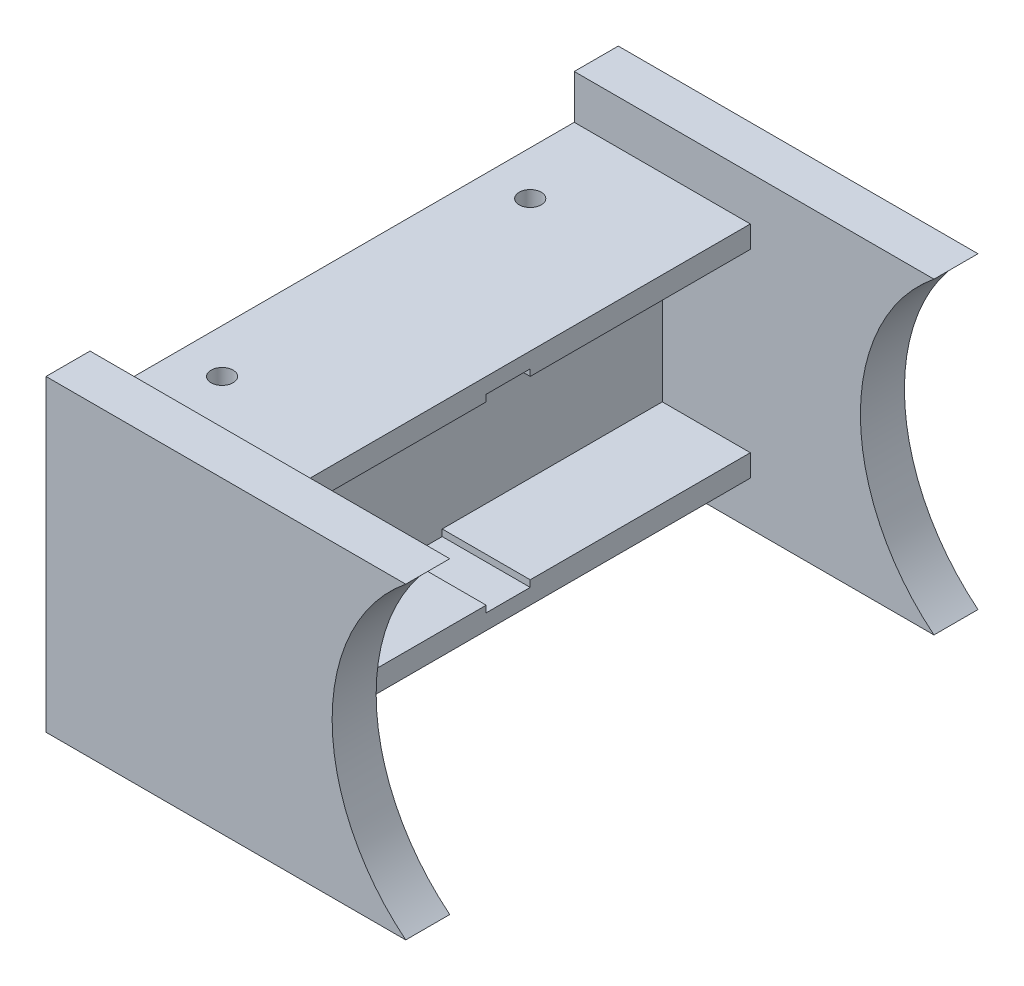
SolidWorks part; units mm, degrees
note: The reader was unsure of these and kept them because the rebuilt part matched: shared geometry of "Sketch1<3>".
ref_plane "Front Plane" through (0, 0, 0) normal (0, 0, 1) x (1, 0, 0)
ref_plane "Top Plane" through (0, 0, 0) normal (0, 1, 0) x (1, 0, 0)
ref_plane "Right Plane" through (0, 0, 0) normal (1, 0, 0) x (0, 0, -1)
sketch "Sketch1" plane through (0, 0, 0) normal (1, 0, 0) x (0, 0, -1)
  line L0 (-3.175, -13.6525) -> (0, -13.6525)
  line L1 (3.175, -13.6525) -> (0, -13.6525)
  line L2 (3.175, 13.6525) -> (0, 13.6525)
  line L3 (-3.175, 13.6525) -> (0, 13.6525)
  line L4 (-3.175, 12.7) -> (-34.925, 12.7)
  line L5 (-34.925, 12.7) -> (-34.925, -12.7)
  line L6 (-34.925, -12.7) -> (-3.175, -12.7)
  line L7 (-3.175, 12.7) -> (-3.175, 13.6525)
  line L8 (3.175, 12.7) -> (3.175, 13.6525)
  line L9 (3.175, -13.6525) -> (3.175, -12.7)
  line L10 (-3.175, -13.6525) -> (-3.175, -12.7)
  line L11 (3.175, -12.7) -> (34.925, -12.7)
  line L12 (34.925, -12.7) -> (34.925, 12.7)
  line L13 (34.925, 12.7) -> (3.175, 12.7)
  line L14 (-34.925, 12.7) -> (-34.925, 15.875)
  line L15 (-34.925, 15.875) -> (34.925, 15.875)
  line L16 (34.925, 15.875) -> (34.925, 12.7)
  line L17 (34.925, -12.7) -> (34.925, -15.875)
  line L18 (34.925, -15.875) -> (-34.925, -15.875)
  line L19 (-34.925, -15.875) -> (-34.925, -12.7)
  dimension "D2" = 3.175
extrude "Boss-Extrude1" add sketch "Sketch1" along normal blind 12.7 contours L16 L15 L14 L4 L7 L3 L2 L8 L13 | L19 L18 L17 L11 L9 L1 L0 L10 L6
extrude "Boss-Extrude2" add sketch "Sketch1<3>" against normal blind 12.7 contours L16 L15 L14 L4 L7 L3 L2 L8 L13 | L12 L13 L8 L2 L3 L7 L4 L5 L6 L10 L0 L1 L9 L11 | L19 L18 L17 L11 L9 L1 L0 L10 L6
sketch "Sketch1<3>" plane through (0, 0, 0) normal (1, 0, 0) x (0, 0, -1) same geometry as "Sketch1"
sketch "Sketch3" plane through (0, 0, -34.925) normal (0, 0, -1) x (-1, 0, 0)
  line L0 (12.7, 15.875) -> (12.7, -15.875) construction
  line L1 (12.7, -22.225) -> (-44.45, -22.225)
  line L2 (12.7, -22.225) -> (12.7, 22.225)
  line L3 (12.7, 22.225) -> (-44.45, 22.225)
  line L4 (-44.45, -22.225) -> (-44.45, 22.225)
  circle A1 centre (-57.15, 0) radius 28.575
  point P4 (12.7, 0)
  dimension "D3" = 57.15
  dimension "D1" = 44.45
  dimension "D2" = 57.15
  dimension "D4" = 69.85
extrude "Boss-Extrude3" add sketch "Sketch3" along normal blind 6.35
mirror "Mirror1" about plane through (0, 0, 0) normal (0, 0, 1) of "Boss-Extrude3"
sketch "Sketch4" plane through (0, 15.875, 0) normal (0, 1, 0) x (1, 0, 0)
  line L0 (-12.7, -34.925) -> (-12.7, 34.925) construction
  line L1 (-24.4475, 0) -> (24.4475, 0) construction
  circle A0 centre (-6.35, 22.225) radius 1.5875
  circle A1 centre (-6.35, -22.225) radius 1.5875
  dimension "D3" = 3.175
  dimension "D1" = 22.225
  dimension "D2" = 6.35
extrude "Cut-Extrude1" cut sketch "Sketch4" against normal blind 20.32
sketch "Sketch5" plane through (-12.7, 0, 0) normal (-1, 0, 0) x (0, 0, 1)
  line L0 (-22.225, 0) -> (22.225, 0) construction
  line L1 (-22.225, 0) -> (-22.225, 19.4601) construction
  line L2 (34.925, 15.875) -> (-34.925, 15.875) construction
  line L3 (-26.1937, 3.175) -> (-18.2562, 3.175)
  line L4 (-26.1937, 3.175) -> (-26.1937, 6.35)
  line L5 (-26.1937, 6.35) -> (-18.2562, 6.35)
  line L6 (-18.2562, 3.175) -> (-18.2562, 6.35)
  line L7 (0, -24.4475) -> (0, 24.4475) construction
  line L8 (26.1937, 6.35) -> (18.2562, 6.35)
  line L9 (18.2562, 3.175) -> (18.2562, 6.35)
  line L10 (26.1937, 3.175) -> (18.2562, 3.175)
  line L11 (26.1937, 3.175) -> (26.1937, 6.35)
  point P3 (0, 0)
  point P11 (-22.225, 6.35)
  dimension "D1" = 44.45
  dimension "D2" = 7.9375
  dimension "D3" = 12.7
  dimension "D4" = 3.175
extrude "Cut-Extrude2" cut sketch "Sketch5" against normal blind 12.7
